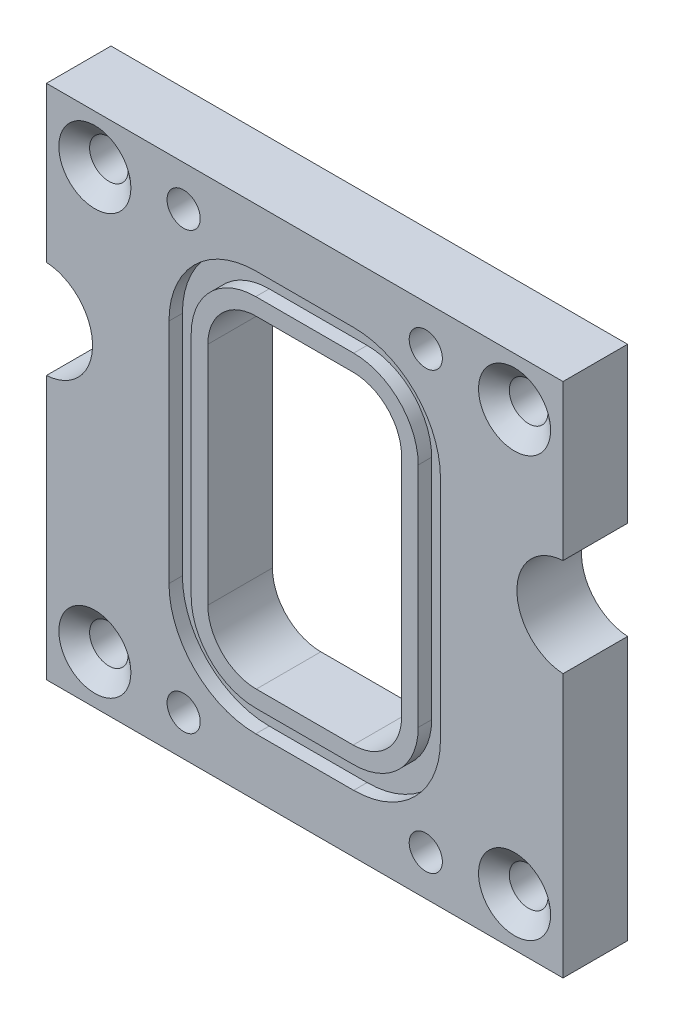
SolidWorks part; units mm, degrees
material "6061 Alloy"
ref_plane "Front Plane" through (0, 0, 0) normal (0, 0, 1) x (1, 0, 0)
ref_plane "Top Plane" through (0, 0, 0) normal (0, 1, 0) x (1, 0, 0)
ref_plane "Right Plane" through (0, 0, 0) normal (1, 0, 0) x (0, 0, -1)
sketch "Sketch1" plane through (0, 0, 0) normal (0, 0, 1) x (1, 0, 0)
  line L1 (-25.4, -25.4) -> (25.4, -25.4)
  line L2 (-25.4, -25.4) -> (-25.4, 25.4)
  line L3 (-25.4, 25.4) -> (25.4, 25.4)
  line L4 (25.4, -25.4) -> (25.4, 25.4)
  line L5 (-25.4, -25.4) -> (25.4, 25.4) construction
  line L6 (-25.4, 25.4) -> (25.4, -25.4) construction
  point P0 (0, 0)
  dimension "D1" = 50.8
  dimension "D2" = 50.8
extrude "Boss-Extrude1" add sketch "Sketch1" along normal blind 6.35
sketch "Sketch2" plane through (0, 0, 6.35) normal (0, 0, 1) x (1, 0, 0)
  line L0 (-4.7625, -15.875) -> (4.7625, -15.875)
  line L1 (-9.525, -11.1125) -> (-9.525, 11.1125)
  line L2 (-4.7625, 15.875) -> (4.7625, 15.875)
  line L3 (9.525, -11.1125) -> (9.525, 11.1125)
  line L4 (-9.525, -15.875) -> (9.525, 15.875) construction
  line L5 (-9.525, 15.875) -> (9.525, -15.875) construction
  line L6 (25.4, 25.4) -> (-25.4, 25.4) construction
  line L7 (-25.4, 25.4) -> (-25.4, -25.4) construction
  arc A0 (-4.7625, -15.875) -> (-9.525, -11.1125) centre (-4.7625, -11.1125) cw
  arc A1 (4.7625, -15.875) -> (9.525, -11.1125) centre (4.7625, -11.1125) ccw
  arc A2 (4.7625, 15.875) -> (9.525, 11.1125) centre (4.7625, 11.1125) cw
  arc A3 (-9.525, 11.1125) -> (-4.7625, 15.875) centre (-4.7625, 11.1125) cw
  point P0 (0, 0)
  point P19 (0, 25.4)
  point P22 (-25.4, 0)
  dimension "D2" = 4.7625
  dimension "D1" = 31.75
  dimension "D3" = 19.05
extrude "Cut-Extrude1" cut sketch "Sketch2" against normal through all
sketch "Sketch3" plane through (0, 0, 6.35) normal (0, 0, 1) x (1, 0, 0)
  line L0 (13.3477, -11.176) -> (13.3477, 11.176)
  line L1 (-4.8133, -17.526) -> (4.8133, -17.526)
  line L2 (-11.1633, -11.176) -> (-11.1633, 11.176)
  line L3 (-4.8133, 17.526) -> (4.8133, 17.526)
  line L4 (11.1633, -11.176) -> (11.1633, 11.176)
  line L5 (-11.1633, -17.526) -> (11.1633, 17.526) construction
  line L6 (-11.1633, 17.526) -> (11.1633, -17.526) construction
  line L7 (-4.8133, -19.7104) -> (4.8133, -19.7104)
  line L8 (-13.3477, -11.176) -> (-13.3477, 11.176)
  line L9 (-4.8133, 19.7104) -> (4.8133, 19.7104)
  arc A0 (-4.8133, -17.526) -> (-11.1633, -11.176) centre (-4.8133, -11.176) cw
  arc A1 (4.8133, -17.526) -> (11.1633, -11.176) centre (4.8133, -11.176) ccw
  arc A2 (4.8133, 17.526) -> (11.1633, 11.176) centre (4.8133, 11.176) cw
  arc A3 (-11.1633, 11.176) -> (-4.8133, 17.526) centre (-4.8133, 11.176) cw
  arc A4 (4.8133, 19.7104) -> (13.3477, 11.176) centre (4.8133, 11.176) cw
  arc A5 (4.8133, -19.7104) -> (13.3477, -11.176) centre (4.8133, -11.176) ccw
  arc A6 (-4.8133, -19.7104) -> (-13.3477, -11.176) centre (-4.8133, -11.176) cw
  arc A7 (-13.3477, 11.176) -> (-4.8133, 19.7104) centre (-4.8133, 11.176) cw
  point P0 (0, 0)
  dimension "D1" = 6.35
  dimension "D2" = 9.6266
  dimension "D3" = 22.352
  dimension "D4" = 2.1844
extrude "Cut-Extrude2 - dash 027" cut sketch "Sketch3" against normal blind 1.3208
hole_wizard "CSK for #6 Flat Head Machine Screw (100)1" positions "Sketch5" profile "Sketch4" countersink size "#6" standard "Ansi Inch" end condition through all
sketch "Sketch5" plane through (0, 0, 6.35) normal (0, 0, 1) x (1, 0, 0)
  line L0 (-25.4, 25.4) -> (-25.4, -25.4) construction
  line L1 (25.4, 25.4) -> (-25.4, 25.4) construction
  line L2 (-25.4, -25.4) -> (25.4, -25.4) construction
  line L3 (25.4, -25.4) -> (25.4, 25.4) construction
  point P0 (-20.6375, 20.6375)
  point P1 (20.6375, 20.6375)
  point P3 (20.6375, -20.6375)
  point P5 (-20.6375, -20.6375)
  dimension "D1" = 4.7625
  dimension "D2" = 4.7625
  dimension "D3" = 4.7625
  dimension "D4" = 4.7625
sketch "Sketch4" plane through (-20.6375, 20.6375, 6.35) normal (1, 0, 0) x (0, -1, 0)
  line L0 (0, 0) -> (0, 6.35)
  line L1 (0, 6.35) -> (1.8986, 6.35)
  line L2 (1.8986, 6.35) -> (1.8986, 1.38)
  line L3 (1.8986, 1.38) -> (3.5433, 0)
  line L5 (3.5433, 0) -> (0, 0)
  line L6 (-1.8986, 1.38) -> (-3.5433, 0) construction
  line L11 (0, -6.35) -> (0, 107.95) construction
  dimension "Thru Hole Dia." = 3.7973
  dimension "Thru Hole Depth" = 6.35
  dimension "Near C'Sink Dia." = 7.0866
  dimension "Near C'Sink Angle" = 100
hole_wizard "CSK for #4 Flat Head Machine Screw (100)1" positions "Sketch7" profile "Sketch6" countersink size "#4" standard "Ansi Inch" end condition through all
sketch "Sketch7" plane through (0, 0, 0) normal (0, 0, -1) x (-1, 0, 0)
  line L0 (-25.4, 25.4) -> (25.4, 25.4) construction
  line L1 (25.4, -25.4) -> (-25.4, -25.4) construction
  line L2 (25.4, 25.4) -> (25.4, -25.4) construction
  line L3 (-25.4, -25.4) -> (-25.4, 25.4) construction
  point P0 (-11.9062, 21.4312)
  point P1 (11.9062, 21.4312)
  point P3 (-11.9062, -21.4313)
  point P5 (11.9062, -21.4313)
  dimension "D1" = 3.9688
  dimension "D2" = 3.9688
  dimension "D3" = 13.4937
  dimension "D4" = 13.4937
sketch "Sketch6" plane through (11.9062, 21.4312, 0) normal (1, 0, 0) x (0, 1, 0)
  line L0 (0, 0) -> (0, 6.35)
  line L1 (0, 6.35) -> (1.6319, 6.35)
  line L2 (1.6319, 6.35) -> (1.6319, 1.8481)
  line L3 (1.6319, 1.8481) -> (3.2385, 0)
  line L5 (3.2385, 0) -> (0, 0)
  line L6 (-1.6319, 1.8481) -> (-3.2385, 0) construction
  line L11 (0, -6.35) -> (0, 107.95) construction
  dimension "Thru Hole Dia." = 3.2639
  dimension "Thru Hole Depth" = 6.35
  dimension "Near C'Sink Dia." = 6.477
  dimension "Near C'Sink Angle" = 82
ref_plane "Plane1" through (0, 0, 3.175) normal (0, 0, -1) x (-1, 0, 0)
mirror "Mirror1" about plane through (0, 0, 3.175) normal (0, 0, -1) of "Cut-Extrude2 - dash 027"
sketch "Sketch8" plane through (0, 0, 6.35) normal (0, 0, 1) x (1, 0, 0)
  line L0 (25.4, 25.4) -> (-25.4, 25.4) construction
  circle A0 centre (-25.6921, 5.334) radius 4.826
  dimension "D1" = 20.066
  dimension "D3" = 9.652
  dimension "D2" = 25.6921
extrude "Cut-Extrude2" cut sketch "Sketch8" against normal through all
mirror "Mirror2" about plane through (0, 0, 0) normal (1, 0, 0) of "Cut-Extrude2"
